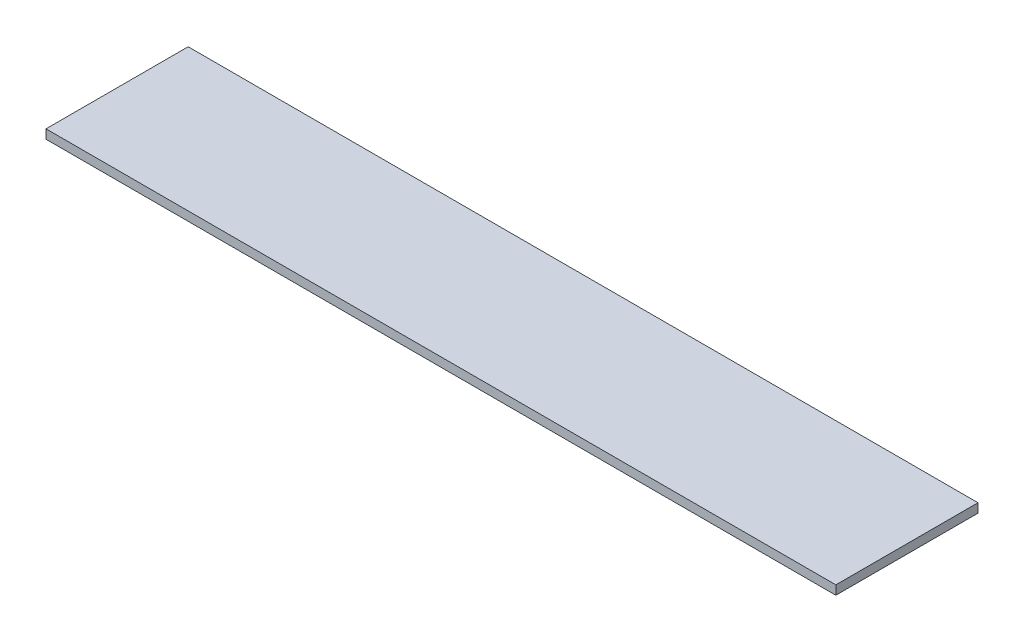
SolidWorks part; units mm, degrees
ref_plane "Front Plane" through (0, 0, 0) normal (0, 0, 1) x (1, 0, 0)
ref_plane "Top Plane" through (0, 0, 0) normal (0, 1, 0) x (1, 0, 0)
ref_plane "Right Plane" through (0, 0, 0) normal (1, 0, 0) x (0, 0, -1)
sketch "Sketch1" plane through (0, 0, 0) normal (0, 1, 0) x (1, 0, 0)
  line L1 (-175, -31.5) -> (175, -31.5)
  line L2 (-175, -31.5) -> (-175, 31.5)
  line L3 (-175, 31.5) -> (175, 31.5)
  line L4 (175, -31.5) -> (175, 31.5)
  line L5 (-175, -31.5) -> (175, 31.5) construction
  line L6 (-175, 31.5) -> (175, -31.5) construction
  point P0 (0, 0)
  dimension "D1" = 350
  dimension "D2" = 63
base flange "Base-Flange1" sketch "Sketch1" thickness 4 reverse thickness direction no parameters "D1"=0.5
sketch "Bend-Lines1" plane through (0, 0, 0) normal (0, 1, 0) x (1, 0, 0)
sketch "Bounding-Box1" plane through (0, 0, 0) normal (0, 1, 0) x (1, 0, 0)
sheet metal parameters "Sheet-Metal(1)" thickness 4 parameters "D1"=0.5
flat pattern "Flat-Pattern(1)" [suppressed]
sketch "Bend-Lines2" plane through (0, 0, 0) normal (0, 1, 0) x (1, 0, 0)
sketch "Bounding-Box2" [suppressed] plane through (0, 0, 0) normal (0, 1, 0) x (1, 0, 0)
